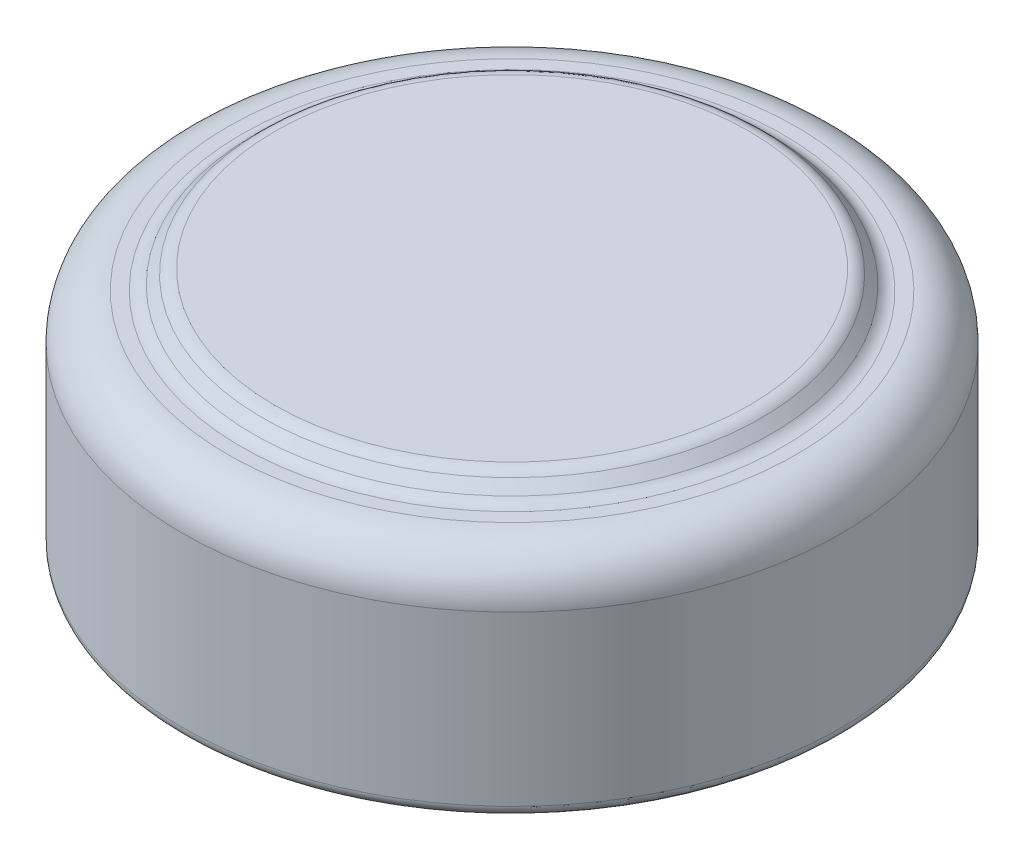
SolidWorks part; units mm, degrees
ref_plane "Front Plane" through (0, 0, 0) normal (0, 0, 1) x (1, 0, 0)
ref_plane "Top Plane" through (0, 0, 0) normal (0, 1, 0) x (1, 0, 0)
ref_plane "Right Plane" through (0, 0, 0) normal (1, 0, 0) x (0, 0, -1)
sketch "Sketch1" plane through (0, 0, 0) normal (0, 0, 1) x (1, 0, 0)
  line L0 (0, 0) -> (-2.8, 0)
  line L1 (-2.9, 0.1) -> (-2.9, 1.58)
  line L2 (-2.0879, 2.15) -> (0, 2.15)
  line L3 (0, 2.15) -> (0, 0)
  line L4 (-2.2761, 2.0239) -> (-2.1939, 2.1061)
  line L7 (-2.3821, 1.98) -> (-2.5, 1.98)
  arc A0 (-2.9, 1.58) -> (-2.5, 1.98) centre (-2.5, 1.58) cw
  arc A1 (-2.0879, 2.15) -> (-2.1939, 2.1061) centre (-2.0879, 2) ccw
  arc A2 (-2.3821, 1.98) -> (-2.2761, 2.0239) centre (-2.3821, 2.13) ccw
  arc A3 (-2.8, 0) -> (-2.9, 0.1) centre (-2.8, 0.1) cw
  point P9 (-2.9, 1.98)
  point P13 (-2.32, 1.98)
  point P17 (-2.9, 0)
  point P18 (-2.32, 1.98)
  point P20 (-2.32, 1.98)
  dimension "D6" = 0.4
  dimension "D7" = 0.15
  dimension "D8" = 0.1
  dimension "D1" = 2.9
  dimension "D2" = 2.15
  dimension "D3" = 2.32
  dimension "D4" = 1.98
  dimension "D5" = 45
revolve "Revolve1" add sketch "Sketch1" angle 360 about L3
sketch "Sketch2" plane through (0, 0, 0) normal (0, -1, 0) x (1, 0, 0)
  line L0 (0.25, 0.25) -> (1.4, 0.25)
  line L1 (-0.25, 1.4) -> (0.25, 1.4)
  line L2 (-0.25, 1.4) -> (-0.25, 0.25)
  line L3 (-0.25, -1.4) -> (0.25, -1.4)
  line L4 (0.25, 1.4) -> (0.25, 0.25)
  line L5 (-1.4, 0.25) -> (-0.25, 0.25)
  line L6 (-1.4, 0.25) -> (-1.4, -0.25)
  line L7 (-1.4, -0.25) -> (-0.25, -0.25)
  line L8 (1.4, 0.25) -> (1.4, -0.25)
  line L9 (0.25, -0.25) -> (1.4, -0.25)
  line L10 (0.25, -0.25) -> (0.25, -1.4)
  line L11 (-0.25, -0.25) -> (-0.25, -1.4)
  circle A0 centre (0, 0) radius 1.75 construction
  text T0 "                   SR63" font "Century Gothic" height 0.75
  dimension "D1" = 3.5
  dimension "D2" = 0.5
  dimension "D3" = 0.5
  dimension "D4" = 0.25
  dimension "D5" = 0.25
  dimension "D6" = 2.8
  dimension "D7" = 2.8
  dimension "D8" = 1.4
  dimension "D9" = 1.4
wrap "Wrap1" sketch "Sketch2" wrap type scribe source sketch "Sketch2" face at (-2.8, 0, 0)
